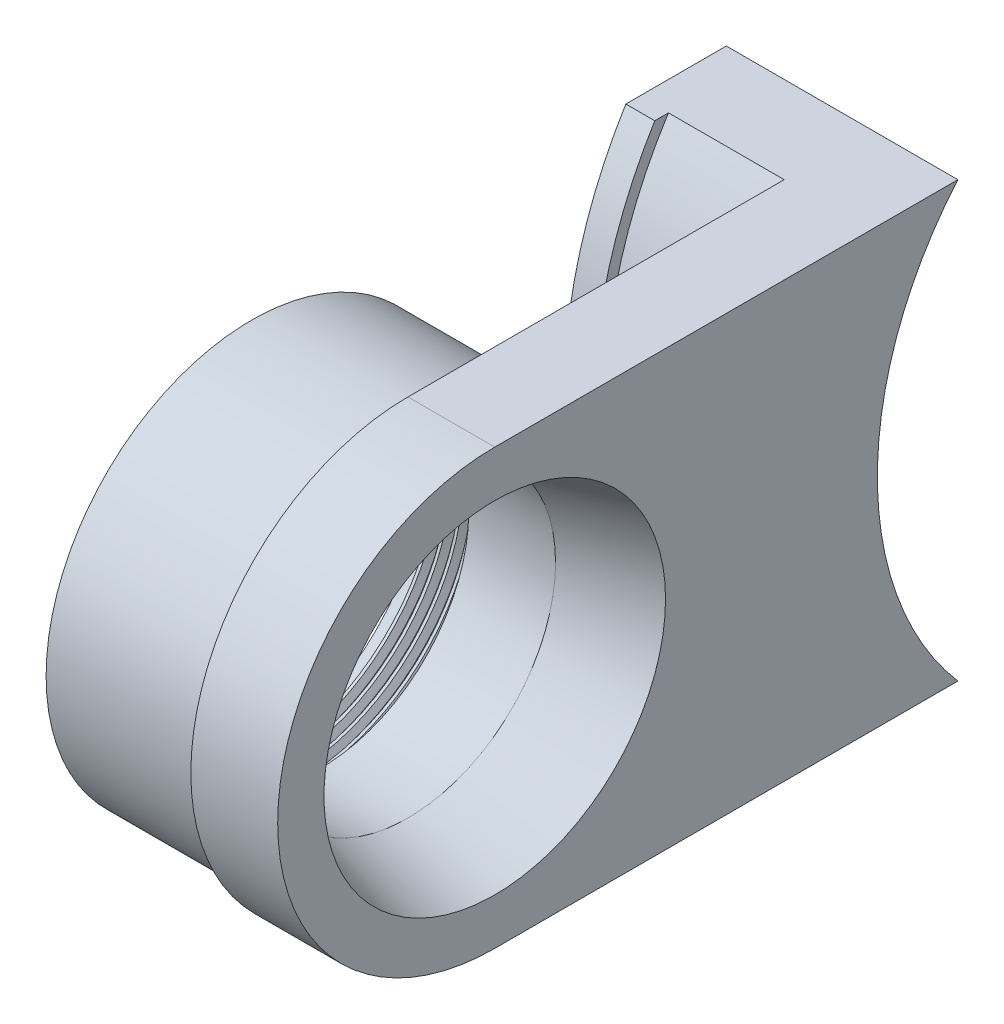
SolidWorks part; units mm, degrees
ref_plane "Front Plane" through (0, 0, 0) normal (0, 0, 1) x (1, 0, 0)
ref_plane "Top Plane" through (0, 0, 0) normal (0, 1, 0) x (1, 0, 0)
ref_plane "Right Plane" through (0, 0, 0) normal (1, 0, 0) x (0, 0, -1)
sketch "Sketch1" plane through (0, 0, 0) normal (1, 0, 0) x (0, 0, -1)
  line L1 (0, 37.5) -> (-80, 37.5)
  line L2 (-80, -37.5) -> (0, -37.5)
  line L3 (0, 37.5) -> (0, -37.5) construction
  line L4 (-80, 37.5) -> (-80, -37.5) construction
  arc A0 (0, 37.5) -> (0, -37.5) centre (43.589, 0) ccw
  arc A1 (-80, 37.5) -> (-80, -37.5) centre (-80, 0) ccw
  circle A2 centre (-80, 0) radius 25.5
  point P3 (0, 0)
  dimension "D1" = 57.5
  dimension "D2" = 51
  dimension "D3" = 75
  dimension "D4" = 80
extrude "Boss-Extrude1" add sketch "Sketch1" along normal blind 15
sketch "Sketch2" plane through (0, 0, 0) normal (-1, 0, 0) x (0, 0, 1)
  line L0 (0, 37.5) -> (15, 37.5)
  line L1 (0, 37.5) -> (80, 37.5) construction
  line L2 (0, -37.5) -> (15, -37.5)
  line L3 (80, -37.5) -> (0, -37.5) construction
  arc A0 (0, -37.5) -> (0, 37.5) centre (-43.589, 0) ccw
  arc A1 (15, -37.5) -> (15, 37.5) centre (-43.589, 0) ccw
  arc A2 (0, -37.5) -> (0, 37.5) centre (-43.589, 0) ccw construction
  dimension "D1" = 15
extrude "Boss-Extrude2" add sketch "Sketch2" along normal blind 20
sketch "Sketch4" plane through (-20, 0, 0) normal (-1, 0, 0) x (0, 0, 1)
  line L0 (0, 37.5) -> (17.3611, 37.5)
  line L1 (0, -37.5) -> (17.3611, -37.5)
  arc A0 (0, 37.5) -> (0, -37.5) centre (-43.589, 0) cw
  arc A1 (0, -37.5) -> (0, 37.5) centre (-43.589, 0) ccw construction
  arc A2 (17.3611, 37.5) -> (17.3611, -37.5) centre (-43.589, 0) cw
  arc A3 (15, -37.5) -> (15, 37.5) centre (-43.589, 0) ccw construction
  dimension "D1" = 2
extrude "Boss-Extrude4" add sketch "Sketch4" along normal blind 5
sketch "Sketch13" plane through (0, 0, 0) normal (0, 1, 0) x (1, 0, 0)
  line L0 (15, -109.5) -> (0, -105.5)
  line L1 (0, -105.5) -> (15, -105.5)
  line L2 (15, -105.5) -> (15, -109.5)
  line L5 (15, -105.5) -> (15, -54.5) construction
  line L6 (15, -105.5) -> (15, -54.5) construction
  line L7 (15, -80) -> (-11.574, -80) construction
  point P11 (0, 0)
  point P12 (0, 0)
  dimension "7\\" = 4
revolve "Cut-Revolve2" cut sketch "Sketch13" angle 360 about L7
sketch "Sketch14" plane through (0, 0, 0) normal (-1, 0, 0) x (0, 0, 1)
  circle A0 centre (80, 0) radius 25.5
  circle A1 centre (80, 0) radius 35.5
  circle A2 centre (80, 0) radius 25.5 construction
  dimension "D1" = 10
extrude "Boss-Extrude5" add sketch "Sketch14" along normal blind 27
sketch "Sketch15" plane through (-27, 0, 0) normal (-1, 0, 0) x (0, 0, 1)
  circle A0 centre (80, 0) radius 25.5
  circle A1 centre (80, 0) radius 30.5
  dimension "D1" = 5
extrude "Cut-Extrude3" cut sketch "Sketch15" against normal blind 12
thread "Thread1" pitch 2 method extrude profile "Thread Profile1" start angle 0, offset 0, length 0, pitch 2, diameter 61
ref_plane "Plane1" through (-27, 0, 49.5) normal (0, -1, 0) x (0, 0, -1)
sketch "Thread Profile1" plane through (-27, 0, 49.5) normal (0, -1, 0) x (0, 0, -1)
  line L0 (0, 0) -> (0, 2) construction
  line L11 (0, 0) -> (0, 1.75)
  line L12 (0, 1.75) -> (-1.0825, 1.125)
  line L13 (-1.0825, 1.125) -> (-1.0825, 0.625)
  line L15 (-1.0825, 0.625) -> (0, 0)
  line L17 (-1.0825, 0.875) -> (0, 0.875) construction
  point P2 (0, 0)
  dimension "Pitch" = 2
  dimension "Profile_Angle" = 60
  dimension "Profile_Land" = 0.5
  dimension "Profile_Height" = 1.0825
